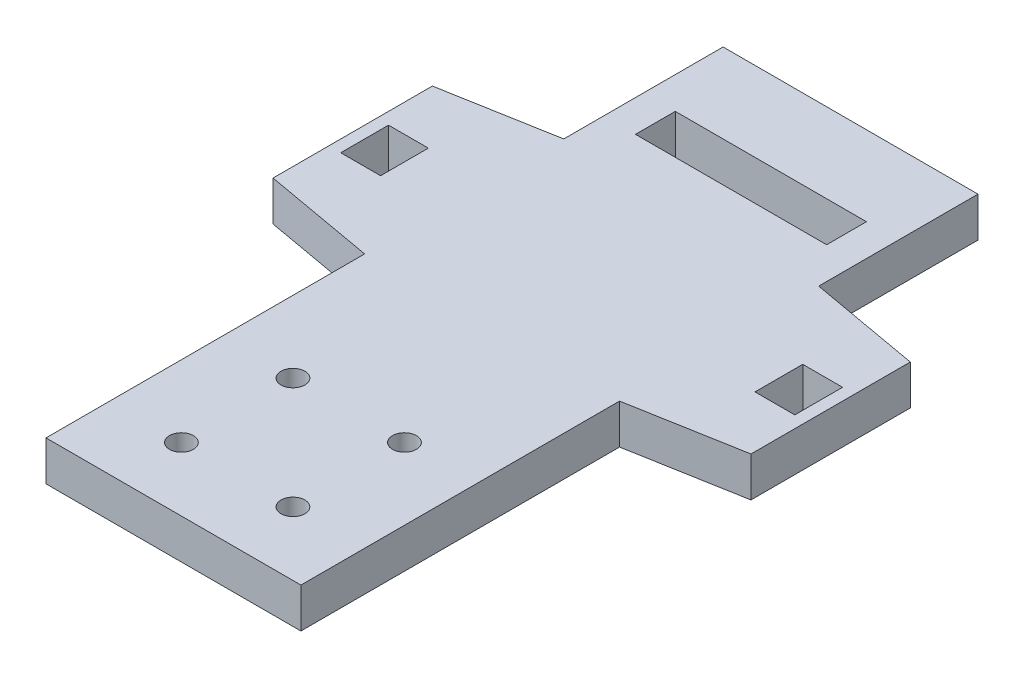
SolidWorks part; units mm, degrees
ref_plane "Front Plane" through (0, 0, 0) normal (0, 0, 1) x (1, 0, 0)
ref_plane "Top Plane" through (0, 0, 0) normal (0, 1, 0) x (1, 0, 0)
ref_plane "Right Plane" through (0, 0, 0) normal (1, 0, 0) x (0, 0, -1)
sketch "Sketch1" plane through (0, 0, 0) normal (0, 1, 0) x (1, 0, 0)
  line L0 (-16, -42.5) -> (16, -42.5)
  line L1 (16, -42.5) -> (16, -2.5)
  line L2 (16, -2.5) -> (30, 0)
  line L3 (30, 0) -> (30, 20)
  line L4 (30, 20) -> (16, 22.5)
  line L5 (16, 22.5) -> (16, 42.5)
  line L6 (16, 42.5) -> (-16, 42.5)
  line L7 (-16, 42.5) -> (-16, 22.5)
  line L8 (-16, 22.5) -> (-30, 20)
  line L9 (-30, 20) -> (-30, 0)
  line L10 (-30, 0) -> (-16, -2.5)
  line L11 (-16, -2.5) -> (-16, -42.5)
  point P9 (30, 10)
  dimension "D1" = 40
  dimension "D2" = 40
  dimension "D3" = 32
  dimension "D4" = 32
  dimension "D5" = 60
  dimension "D6" = 20
  dimension "D7" = 20
  dimension "D8" = 14
  dimension "D9" = 14
  dimension "D10" = 16
  dimension "D11" = 85
  dimension "D12" = 42.5
  dimension "D13" = 20
  dimension "D14" = 20
  dimension "D15" = 2.5
  dimension "D16" = 2.5
extrude "Boss-Extrude1" add sketch "Sketch1" along normal blind 5
sketch "Sketch2" plane through (0, 5, 0) normal (0, 1, 0) x (1, 0, 0)
  line L4 (16, -42.5) -> (16, -2.5) construction
  line L5 (-16, 42.5) -> (-16, 22.5) construction
  line L6 (-28.5, 13) -> (-28.5, 7)
  line L7 (-28.5, 7) -> (-23.5, 7)
  line L8 (-23.5, 7) -> (-23.5, 13)
  line L11 (-28.5, 13) -> (-23.5, 13)
  line L12 (-30, 20) -> (-30, 0) construction
  line L13 (23.5, 13) -> (28.5, 13)
  line L14 (28.5, 13) -> (28.5, 7)
  line L15 (28.5, 7) -> (23.5, 7)
  line L16 (23.5, 7) -> (23.5, 13)
  line L17 (30, 0) -> (30, 20) construction
  line L18 (-16, -2.5) -> (-16, -42.5) construction
  line L19 (-16, -42.5) -> (16, -42.5) construction
  line L20 (-12, 32.5) -> (12, 32.5)
  line L21 (-12, 32.5) -> (-12, 27.5)
  line L22 (-12, 27.5) -> (12, 27.5)
  line L23 (12, 32.5) -> (12, 27.5)
  line L24 (16, 42.5) -> (-16, 42.5) construction
  circle A0 centre (-7, -20.5) radius 1.5
  circle A1 centre (7, -20.5) radius 1.5
  circle A2 centre (-7, -34.5) radius 1.5
  circle A3 centre (7, -34.5) radius 1.5
  dimension "D5" = 3
  dimension "D6" = 3
  dimension "D7" = 3
  dimension "D8" = 3
  dimension "D3" = 14
  dimension "D4" = 14
  dimension "D9" = 9
  dimension "D10" = 14
  dimension "D11" = 8
  dimension "D12" = 14
  dimension "D13" = 9
  dimension "D14" = 9
  dimension "D15" = 24
  dimension "D16" = 5
  dimension "D17" = 1.5
  dimension "D18" = 6
  dimension "D19" = 5
  dimension "D20" = 7
  dimension "D21" = 5
  dimension "D22" = 6
  dimension "D23" = 1.5
  dimension "D24" = 7
  dimension "D25" = 4
  dimension "D26" = 10
extrude "Cut-Extrude1" cut sketch "Sketch2" against normal blind 5
